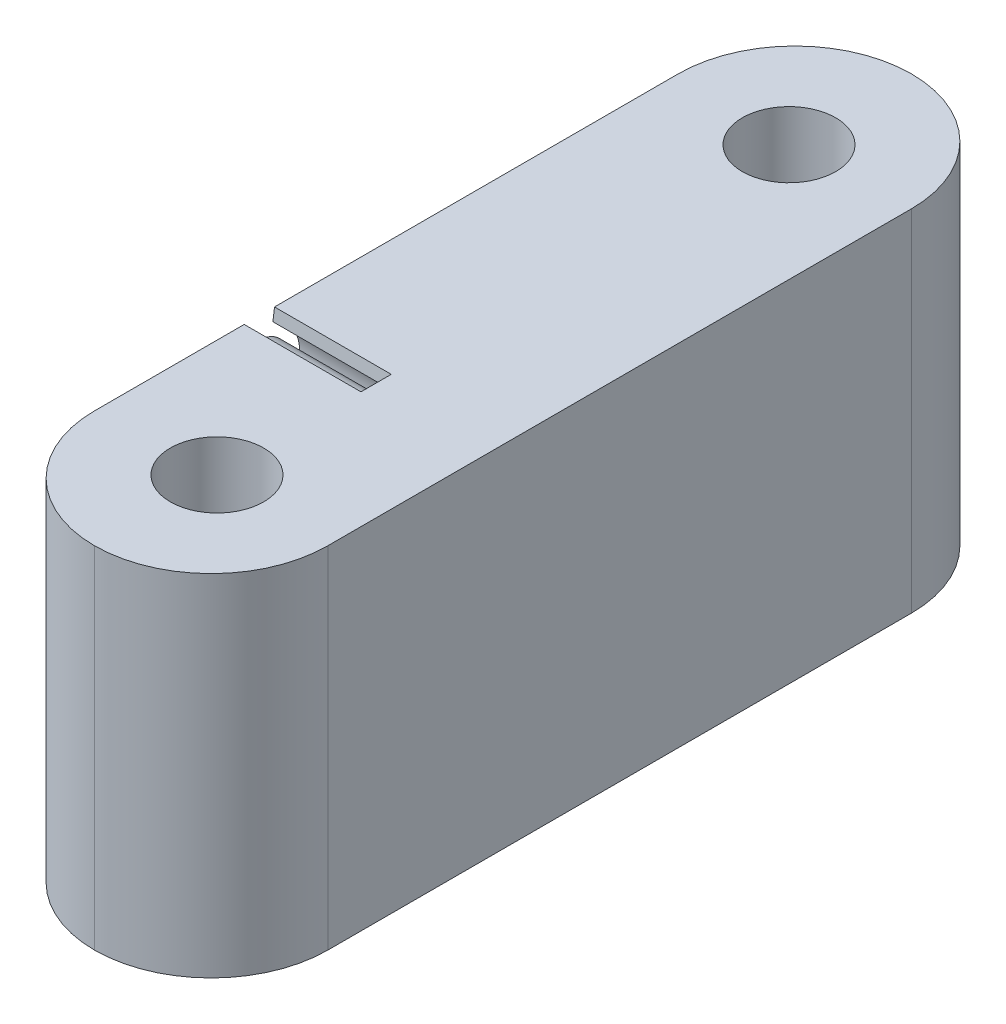
SolidWorks part; units mm, degrees
ref_plane "Front Plane" through (0, 0, 0) normal (0, 0, 1) x (1, 0, 0)
ref_plane "Top Plane" through (0, 0, 0) normal (0, 1, 0) x (1, 0, 0)
ref_plane "Right Plane" through (0, 0, 0) normal (1, 0, 0) x (0, 0, -1)
sketch "Sketch2" plane through (0, 0, 0) normal (0, 1, 0) x (1, 0, 0)
  line L1 (-3.5224, 29.7612) -> (16.4776, 29.7612)
  line L2 (-3.5224, 29.7612) -> (-3.5224, -40.2388)
  line L3 (-3.5224, -40.2388) -> (16.4776, -40.2388)
  line L4 (16.4776, 29.7612) -> (16.4776, -40.2388)
  dimension "D1" = 70
  dimension "D2" = 20
extrude "Boss-Extrude1" add sketch "Sketch2" along normal blind 30
sketch "Sketch3" plane through (0, 30, 0) normal (0, 1, 0) x (1, 0, 0)
  line L1 (-3.5224, -40.2388) -> (16.4776, -40.2388) construction
  line L3 (16.4776, -40.2388) -> (16.4776, 29.7612) construction
  line L4 (16.4776, 29.7612) -> (-3.5224, 29.7612) construction
  circle A0 centre (6.4776, 19.2612) radius 4
  circle A1 centre (6.4776, -29.7388) radius 4
  dimension "D13" = 8
  dimension "D14" = 8
  dimension "D2" = 49
  dimension "D3" = 10.5
  dimension "D4" = 10.5
  dimension "D5" = 10
extrude "Cut-Extrude1" cut sketch "Sketch3" against normal blind 20
sketch "Sketch4" plane through (-3.5224, 0, 0) normal (-1, 0, 0) x (0, 0, 1)
  line L0 (8.1636, 30.0512) -> (8.1636, 15.6029) construction
  line L1 (-23.743, 30.1264) -> (40.1453, 30.1264)
  line L2 (-23.743, 30.1264) -> (-23.743, 15.6782)
  line L3 (-23.743, 15.6782) -> (40.1453, 15.6782)
  line L4 (40.1453, 30.1264) -> (40.1453, 15.6782)
  line L5 (14.95, 28.9694) -> (14.7857, 30.2017)
  line L6 (14.7857, 30.2017) -> (17.4195, 30.2017)
  line L7 (17.4195, 30.2017) -> (17.3442, 28.9224)
  circle A0 centre (16.1636, 25.6866) radius 2.5
  circle A1 centre (16.1636, 25.6866) radius 3.5
  dimension "D2" = 5
  dimension "D3" = 7
  dimension "D1" = 8
extrude "Cut-Extrude2" cut sketch "Sketch4" against normal blind 10
fillet "Fillet1" radius 10 4 edges at (-3.5224, 15, -29.7612) (16.4776, 15, -29.7612) (16.4776, 15, 40.2388) (-3.5224, 15, 40.2388)
